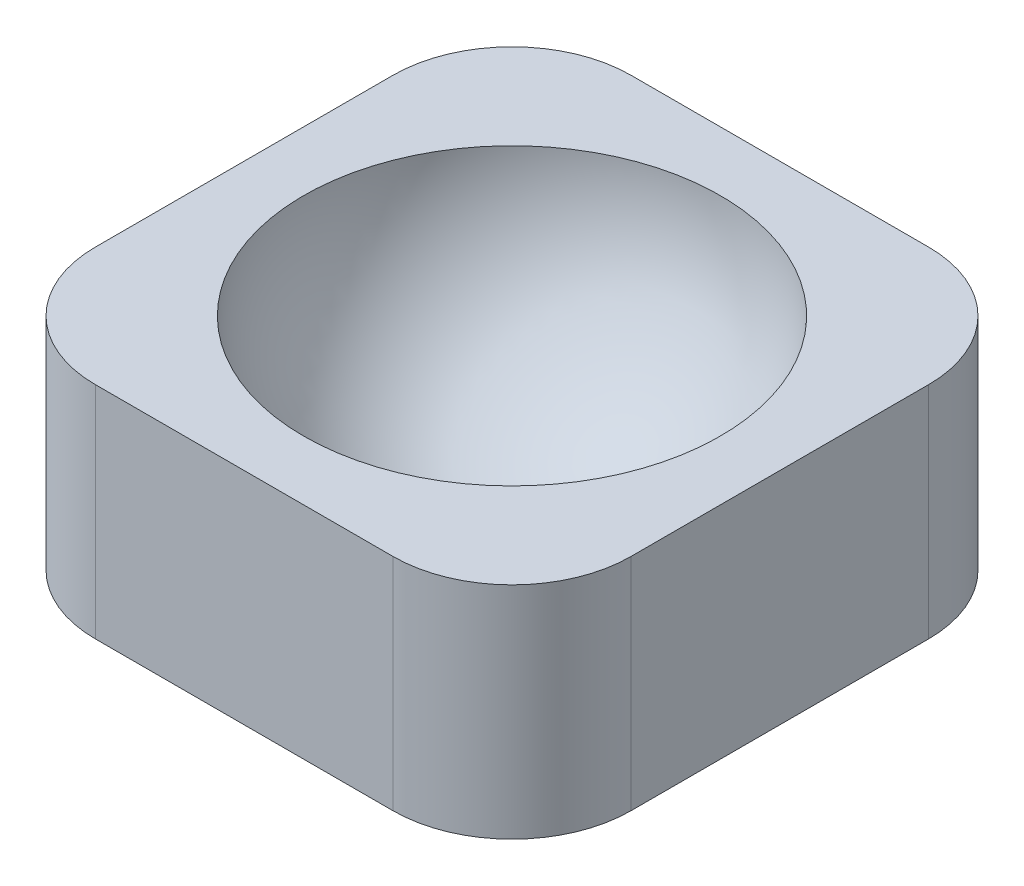
SolidWorks part; units mm, degrees
material "AISI 4340 Steel, normalized"
ref_plane "Front Plane" through (0, 0, 0) normal (0, 0, 1) x (1, 0, 0)
ref_plane "Top Plane" through (0, 0, 0) normal (0, 1, 0) x (1, 0, 0)
ref_plane "Right Plane" through (0, 0, 0) normal (1, 0, 0) x (0, 0, -1)
sketch "Sketch1" plane through (0, 0, 0) normal (0, 1, 0) x (1, 0, 0)
  line L1 (0, 0) -> (-114.3, 0)
  line L2 (0, 0) -> (0, 114.3)
  line L3 (0, 114.3) -> (-114.3, 114.3)
  line L4 (-114.3, 0) -> (-114.3, 114.3)
  circle A0 centre (-57.15, 57.15) radius 44.45
  point P7 (-101.6, 57.15)
  point P8 (-114.3, 57.15)
  point P9 (0, 57.15)
  point P10 (-57.15, 114.3)
  point P11 (-57.15, 0)
  point P13 (-57.15, 101.6)
  dimension "D1" = 88.9
  dimension "D2" = 12.7
  dimension "D3" = 12.7
extrude "Boss-Extrude1" add sketch "Sketch1" along normal blind 46.99 contours L4 L1 L2 L3 A0 | A0 region at (-57.15, 0, -1.6164) region at (-57.15, 0, -57.15)
sketch "Sketch2" plane through (0, 46.99, 0) normal (0, 1, 0) x (1, 0, 0)
  line L0 (-57.15, 114.3) -> (-57.15, 0) construction
  line L1 (0, 114.3) -> (-114.3, 114.3) construction
  line L2 (0, 0) -> (-114.3, 0) construction
  line L3 (-57.15, 101.6) -> (-57.15, 12.7)
  circle A0 centre (-57.15, 57.15) radius 44.45
  dimension "D1" = 88.9
revolve "Cut-Revolve1" cut sketch "Sketch2" angle 180 about L0 region at (-38.2848, 46.99, -57.15) reverse direction yes
fillet "Fillet1" radius 25.4 4 edges at (0, 23.495, 0) (-114.3, 23.495, 0) (-114.3, 23.495, -114.3) (0, 23.495, -114.3)
sketch "Sketch3" plane through (0, 0, 0) normal (0, -1, 0) x (1, 0, 0)
  line L0 (-57.15, -114.3) -> (-57.15, 0) construction
  line L1 (-25.4, -114.3) -> (-88.9, -114.3) construction
  line L2 (-25.4, 0) -> (-88.9, 0) construction
  line L3 (0, -57.15) -> (-114.3, -57.15) construction
  line L4 (0, -25.4) -> (0, -88.9) construction
  line L5 (-114.3, -25.4) -> (-114.3, -88.9) construction
  point P12 (-57.15, -57.15)
equation "\"D3@Sketch1\"=\"D2@Sketch1\""
